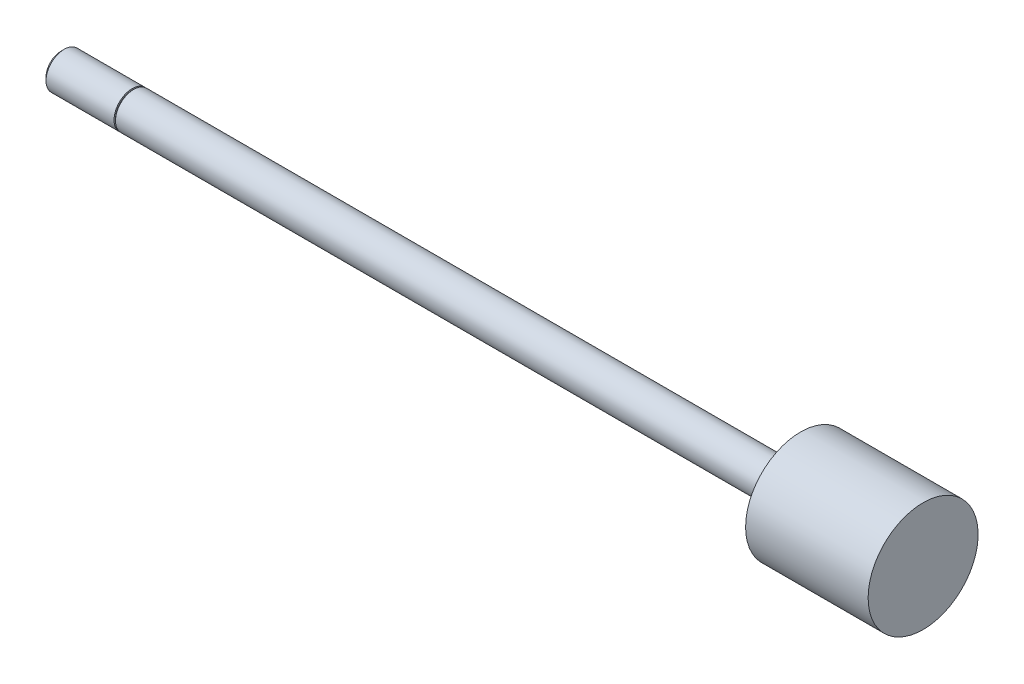
SolidWorks part; units mm, degrees
material "Plain Carbon Steel"
ref_plane "Front Plane" through (0, 0, 0) normal (0, 0, 1) x (1, 0, 0)
ref_plane "Top Plane" through (0, 0, 0) normal (0, 1, 0) x (1, 0, 0)
ref_plane "Right Plane" through (0, 0, 0) normal (1, 0, 0) x (0, 0, -1)
sketch "Sketch1" plane through (0, 0, 0) normal (0, 0, 1) x (1, 0, 0)
  line L0 (0, 0) -> (0, 3.175)
  line L1 (0, 3.175) -> (116.6876, 3.175)
  line L2 (116.6876, 3.175) -> (116.6876, 9.6203)
  line L3 (116.6876, 9.6203) -> (138.1252, 9.6203)
  line L4 (138.1252, 9.6203) -> (138.1252, 0)
  line L5 (138.1252, 0) -> (0, 0)
  line L6 (138.1252, 0) -> (0, 0) construction
revolve "Revolve1" add sketch "Sketch1" angle 360 about L6 reverse direction yes
cosmetic thread "Cosmetic Thread1" parameters "D1"=12.7, "D2"=5.268
sketch "Sketch2" plane through (0, 0, 0) normal (0, 0, 1) x (1, 0, 0)
  line L0 (-12.7, 0) -> (-12.7, 2.634)
  line L1 (-12.7, 2.634) -> (-12.159, 3.175)
  line L2 (-12.159, 3.175) -> (0, 3.175)
  line L3 (0, 3.175) -> (0, 0)
  line L4 (0, 0) -> (-12.7, 0)
  line L5 (0, 0) -> (-12.7, 0) construction
revolve "Revolve2" add sketch "Sketch2" angle 360 about L5 reverse direction yes
ref_plane "Plane1" through (0, 0, 0) normal (1, 0, 0) x (0, 0, -1)
ref_plane "Plane2" through (0, 0, 0) normal (1, 0, 0) x (0, 0, -1)
ref_plane "Plane3" through (254.8128, 0, 0) normal (1, 0, 0) x (0, 0, -1)
ref_plane "Plane4" through (-12.7, 0, 0) normal (1, 0, 0) x (0, 0, -1)
sketch "Sketch3" plane through (0, 0, 0) normal (0, 0, 1) x (1, 0, 0)
  line L0 (-0.254, 3.429) -> (-0.254, 2.921)
  line L1 (-0.254, 2.921) -> (0, 2.921)
  line L2 (0, 2.921) -> (0, 3.429)
  line L3 (0, 3.429) -> (-0.254, 3.429)
  line L4 (0, 0) -> (-0.254, 0) construction
revolve "Cut-Revolve1" cut sketch "Sketch3" angle 360 about L4 reverse direction yes
ref_plane "Plane5" through (0, 0, 0) normal (1, 0, 0) x (0, 0, -1)
ref_plane "Plane6" through (-16.764, 0, 0) normal (1, 0, 0) x (0, 0, -1)
ref_plane "dia1 XY" through (0, 0, 0) normal (1, 0, 0) x (0, 0, -1)
ref_plane "dia1 XZ" through (0, 3.175, 0) normal (0, -1, 0) x (-1, 0, 0)
ref_plane "dia1 YZ" through (0, 0, 0) normal (0, 0, -1) x (-1, 0, 0)
ref_axis "dia1 X" through (0, 3.175, 80.9) along (0, 0, -1)
ref_axis "dia1 Y" through (0, -50, 0) along (0, 1, 0)
ref_axis "dia1 Z" through (80.9, 3.175, 0) along (-1, 0, 0)
sketch3d "dia1"
  point P0 (0, 3.175, 0)
ref_plane "dia12 XY" through (0, 0, 0) normal (1, 0, 0) x (0, 0, -1)
ref_plane "dia12 XZ" through (0, 0, 0) normal (0, -1, 0) x (-1, 0, 0)
ref_plane "dia12 YZ" through (0, 0, 10.9537) normal (0, 0, -1) x (-1, 0, 0)
ref_axis "dia12 X" through (0, 0, 80.9) along (0, 0, -1)
ref_axis "dia12 Y" through (0, -50, 10.9537) along (0, 1, 0)
ref_axis "dia12 Z" through (80.9, 0, 10.9537) along (-1, 0, 0)
sketch3d "dia12"
  point P0 (0, 0, 10.9537)
ref_plane "dia2 XY" through (0, 0, 0) normal (1, 0, 0) x (0, 0, -1)
ref_plane "dia2 XZ" through (0, -3.175, 0) normal (0, -1, 0) x (-1, 0, 0)
ref_plane "dia2 YZ" through (0, 0, 0) normal (0, 0, -1) x (-1, 0, 0)
ref_axis "dia2 X" through (0, -3.175, 80.9) along (0, 0, -1)
ref_axis "dia2 Y" through (0, -50, 0) along (0, 1, 0)
ref_axis "dia2 Z" through (80.9, -3.175, 0) along (-1, 0, 0)
sketch3d "dia2"
  point P0 (0, -3.175, 0)
ref_plane "dia22 XY" through (0, 0, 0) normal (1, 0, 0) x (0, 0, -1)
ref_plane "dia22 XZ" through (0, 0, 0) normal (0, -1, 0) x (-1, 0, 0)
ref_plane "dia22 YZ" through (0, 0, -10.9537) normal (0, 0, -1) x (-1, 0, 0)
ref_axis "dia22 X" through (0, 0, 80.9) along (0, 0, -1)
ref_axis "dia22 Y" through (0, -50, -10.9537) along (0, 1, 0)
ref_axis "dia22 Z" through (80.9, 0, -10.9537) along (-1, 0, 0)
sketch3d "dia22"
  point P0 (0, 0, -10.9537)
ref_plane "rl1 XY" through (-12.7, 0, 0) normal (1, 0, 0) x (0, 0, -1)
ref_plane "rl1 XZ" through (0, 0, 0) normal (0, -1, 0) x (-1, 0, 0)
ref_plane "rl1 YZ" through (0, 0, 0) normal (0, 0, -1) x (-1, 0, 0)
ref_axis "rl1 X" through (-12.7, 0, 80.9) along (0, 0, -1)
ref_axis "rl1 Y" through (-12.7, -50, 0) along (0, 1, 0)
ref_axis "rl1 Z" through (80.9, 0, 0) along (-1, 0, 0)
sketch3d "rl1"
  point P0 (-12.7, 0, 0)
ref_plane "rl2 XY" through (0, 0, 0) normal (1, 0, 0) x (0, 0, -1)
ref_plane "rl2 XZ" through (0, 0, 0) normal (0, -1, 0) x (-1, 0, 0)
ref_plane "rl2 YZ" through (0, 0, 0) normal (0, 0, -1) x (-1, 0, 0)
ref_axis "rl2 X" through (0, 0, 80.9) along (0, 0, -1)
ref_axis "rl2 Y" through (0, -50, 0) along (0, 1, 0)
ref_axis "rl2 Z" through (80.9, 0, 0) along (-1, 0, 0)
sketch3d "rl2"
  point P0 (0, 0, 0)
ref_plane "rod_cp XY" through (0, 0, 0) normal (1, 0, 0) x (0, 0, -1)
ref_plane "rod_cp XZ" through (0, 0, 0) normal (0, -1, 0) x (-1, 0, 0)
ref_plane "rod_cp YZ" through (0, 0, 0) normal (0, 0, -1) x (-1, 0, 0)
ref_axis "rod_cp X" through (0, 0, 80.9) along (0, 0, -1)
ref_axis "rod_cp Y" through (0, -50, 0) along (0, 1, 0)
ref_axis "rod_cp Z" through (80.9, 0, 0) along (-1, 0, 0)
sketch3d "rod_cp"
  point P0 (0, 0, 0)
ref_plane "thd1 XY" through (-12.7, 0, 0) normal (1, 0, 0) x (0, 0, -1)
ref_plane "thd1 XZ" through (0, 3.175, 0) normal (0, -1, 0) x (-1, 0, 0)
ref_plane "thd1 YZ" through (0, 0, 0) normal (0, 0, -1) x (-1, 0, 0)
ref_axis "thd1 X" through (-12.7, 3.175, 80.9) along (0, 0, -1)
ref_axis "thd1 Y" through (-12.7, -50, 0) along (0, 1, 0)
ref_axis "thd1 Z" through (80.9, 3.175, 0) along (-1, 0, 0)
sketch3d "thd1"
  point P0 (-12.7, 3.175, 0)
ref_plane "thd2 XY" through (-12.7, 0, 0) normal (1, 0, 0) x (0, 0, -1)
ref_plane "thd2 XZ" through (0, -3.175, 0) normal (0, -1, 0) x (-1, 0, 0)
ref_plane "thd2 YZ" through (0, 0, 0) normal (0, 0, -1) x (-1, 0, 0)
ref_axis "thd2 X" through (-12.7, -3.175, 80.9) along (0, 0, -1)
ref_axis "thd2 Y" through (-12.7, -50, 0) along (0, 1, 0)
ref_axis "thd2 Z" through (80.9, -3.175, 0) along (-1, 0, 0)
sketch3d "thd2"
  point P0 (-12.7, -3.175, 0)
ref_plane "to_rod_clevis XY" through (-16.764, 0, 0) normal (1, 0, 0) x (0, 0, -1)
ref_plane "to_rod_clevis XZ" through (0, 0, 0) normal (0, -1, 0) x (-1, 0, 0)
ref_plane "to_rod_clevis YZ" through (0, 0, 0) normal (0, 0, -1) x (-1, 0, 0)
ref_axis "to_rod_clevis X" through (-16.764, 0, 80.9) along (0, 0, -1)
ref_axis "to_rod_clevis Y" through (-16.764, -50, 0) along (0, 1, 0)
ref_axis "to_rod_clevis Z" through (80.9, 0, 0) along (-1, 0, 0)
sketch3d "to_rod_clevis"
  point P0 (-16.764, 0, 0)
